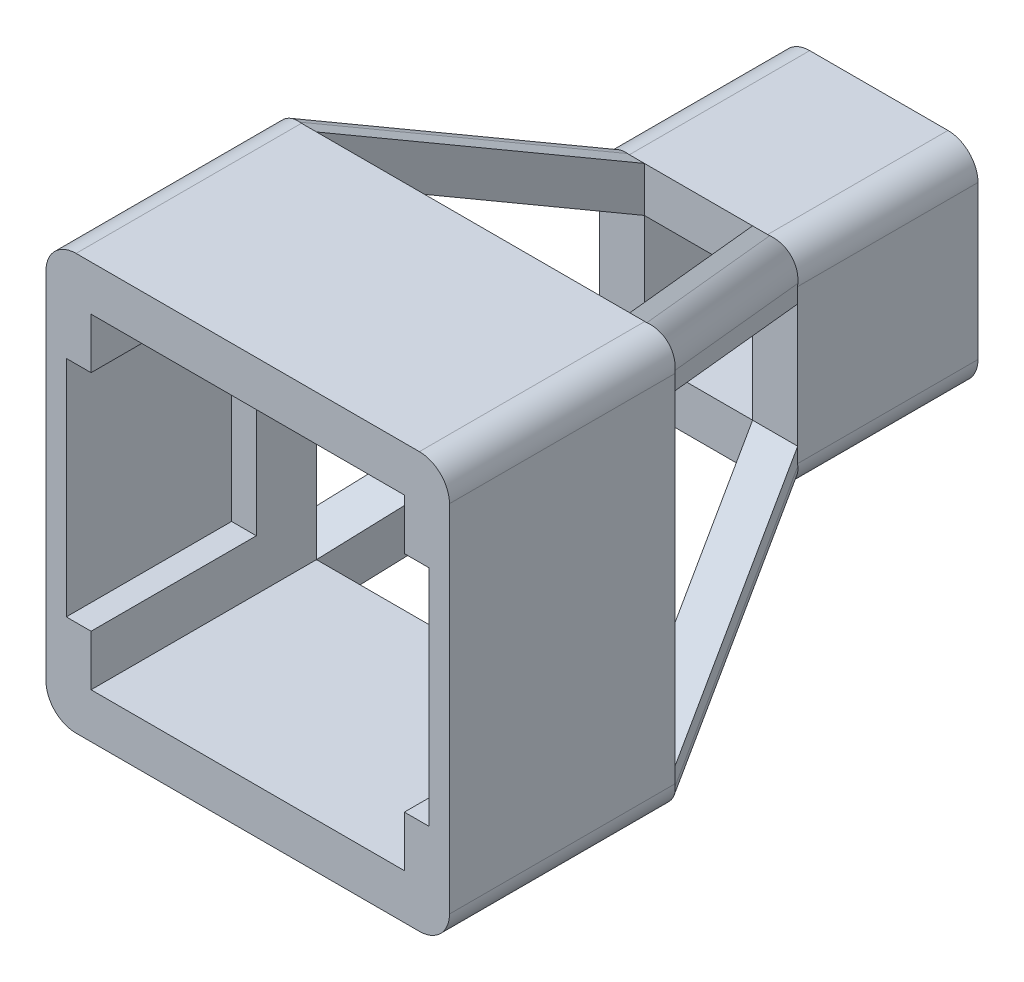
SolidWorks part; units mm, degrees
ref_plane "正面" through (0, 0, 0) normal (0, 0, 1) x (1, 0, 0)
ref_plane "平面" through (0, 0, 0) normal (0, 1, 0) x (1, 0, 0)
ref_plane "右側面" through (0, 0, 0) normal (1, 0, 0) x (0, 0, -1)
sketch "ｽｹｯﾁ1" plane through (0, 0, 0) normal (0, 0, 1) x (1, 0, 0)
  line L0 (6.6, 7.1) -> (-6.6, 7.1)
  line L1 (3.6, -4.1) -> (-3.6, -4.1)
  line L2 (3.6, -4.1) -> (3.6, 4.1)
  line L3 (3.6, 4.1) -> (-3.6, 4.1)
  line L4 (-3.6, -4.1) -> (-3.6, 4.1)
  line L5 (3.6, -4.1) -> (-3.6, 4.1) construction
  line L6 (3.6, 4.1) -> (-3.6, -4.1) construction
  line L7 (-6.6, -7.1) -> (-6.6, 7.1)
  line L8 (6.6, -7.1) -> (-6.6, -7.1)
  line L9 (6.6, -7.1) -> (6.6, 7.1)
  point P0 (0, 0)
  dimension "D1" = 7.2
  dimension "D2" = 8.2
  dimension "D3" = 3
extrude "ﾎﾞｽ - 押し出し1" add sketch "ｽｹｯﾁ1" along normal blind 12
ref_plane "平面1" through (0, 0, 27) normal (0, 0, 1) x (1, 0, 0)
sketch "ｽｹｯﾁ2" plane through (0, 0, 27) normal (0, 0, 1) x (1, 0, 0)
  line L1 (13.425, -14.65) -> (-13.425, -14.65)
  line L2 (13.425, -14.65) -> (13.425, 13)
  line L3 (13.425, 13) -> (-13.425, 13)
  line L4 (-13.425, -14.65) -> (-13.425, 13)
  line L5 (13.425, -14.65) -> (-13.425, 13) construction
  line L6 (13.425, 13) -> (-13.425, -14.65) construction
  line L7 (10.425, -11.65) -> (-10.425, -11.65)
  line L8 (10.425, -11.65) -> (10.425, 10)
  line L9 (10.425, 10) -> (-10.425, 10)
  line L10 (-10.425, -11.65) -> (-10.425, 10)
  line L11 (10.425, -11.65) -> (-10.425, 10) construction
  line L12 (10.425, 10) -> (-10.425, -11.65) construction
  line L13 (-13.425, 13) -> (-10.425, 13)
  line L14 (-13.425, 13) -> (-13.425, 10)
  line L15 (-13.425, 10) -> (-10.425, 10)
  line L16 (-10.425, 13) -> (-10.425, 10)
  line L17 (-13.425, 13) -> (-10.425, 10) construction
  line L18 (-13.425, 10) -> (-10.425, 13) construction
  line L19 (13.425, 13) -> (10.425, 13)
  line L20 (13.425, 13) -> (13.425, 10)
  line L21 (13.425, 10) -> (10.425, 10)
  line L22 (10.425, 13) -> (10.425, 10)
  line L23 (13.425, 13) -> (10.425, 10) construction
  line L24 (13.425, 10) -> (10.425, 13) construction
  line L25 (10.425, -11.65) -> (13.425, -11.65)
  line L26 (10.425, -11.65) -> (10.425, -14.65)
  line L27 (10.425, -14.65) -> (13.425, -14.65)
  line L28 (13.425, -11.65) -> (13.425, -14.65)
  line L29 (10.425, -11.65) -> (13.425, -14.65) construction
  line L30 (10.425, -14.65) -> (13.425, -11.65) construction
  line L31 (-13.425, -14.65) -> (-10.425, -14.65)
  line L32 (-13.425, -14.65) -> (-13.425, -11.65)
  line L33 (-13.425, -11.65) -> (-10.425, -11.65)
  line L34 (-10.425, -14.65) -> (-10.425, -11.65)
  line L35 (-13.425, -14.65) -> (-10.425, -11.65) construction
  line L36 (-13.425, -11.65) -> (-10.425, -14.65) construction
  point P0 (0, 0)
  point P5 (0, 0)
  point P6 (0, 0)
  point P11 (0, 0)
  point P14 (-11.925, 11.5)
  point P15 (0, 0)
  point P18 (11.925, 11.5)
  point P21 (11.925, -13.15)
  point P24 (-11.925, -13.15)
  point P25 (0, 0)
  point P26 (0, 0)
  point P28 (0, -0.825)
  dimension "D1" = 20.85
  dimension "D2" = 21.65
  dimension "D3" = 3
  dimension "D4" = 3
  dimension "D5" = 10
sketch "ｽｹｯﾁ3" plane through (0, 0, 12) normal (0, 0, 1) x (1, 0, 0)
  line L1 (-6.6, 7.1) -> (-3.6, 7.1)
  line L2 (-6.6, 7.1) -> (-6.6, 4.1)
  line L3 (-6.6, 4.1) -> (-3.6, 4.1)
  line L4 (-3.6, 7.1) -> (-3.6, 4.1)
  line L5 (-6.6, 7.1) -> (-3.6, 4.1) construction
  line L6 (-6.6, 4.1) -> (-3.6, 7.1) construction
  line L7 (6.6, 7.1) -> (3.6, 7.1)
  line L8 (6.6, 7.1) -> (6.6, 4.1)
  line L9 (6.6, 4.1) -> (3.6, 4.1)
  line L10 (3.6, 7.1) -> (3.6, 4.1)
  line L11 (6.6, 7.1) -> (3.6, 4.1) construction
  line L12 (6.6, 4.1) -> (3.6, 7.1) construction
  line L13 (6.6, -7.1) -> (3.6, -7.1)
  line L14 (6.6, -7.1) -> (6.6, -4.1)
  line L15 (6.6, -4.1) -> (3.6, -4.1)
  line L16 (3.6, -7.1) -> (3.6, -4.1)
  line L17 (6.6, -7.1) -> (3.6, -4.1) construction
  line L18 (6.6, -4.1) -> (3.6, -7.1) construction
  line L19 (-6.6, -7.1) -> (-3.6, -7.1)
  line L20 (-6.6, -7.1) -> (-6.6, -4.1)
  line L21 (-6.6, -4.1) -> (-3.6, -4.1)
  line L22 (-3.6, -7.1) -> (-3.6, -4.1)
  line L23 (-6.6, -7.1) -> (-3.6, -4.1) construction
  line L24 (-6.6, -4.1) -> (-3.6, -7.1) construction
  point P4 (-5.1, 5.6)
  point P11 (5.1, 5.6)
  point P18 (5.1, -5.6)
  point P25 (-5.1, -5.6)
loft "ﾛﾌﾄ1" add section "ｽｹｯﾁ3" section "ｽｹｯﾁ2" connector at (-3.6, -4.1, 12) connector at (-10.425, -11.65, 27)
loft "ﾛﾌﾄ2" add section "ｽｹｯﾁ3<4>" section "ｽｹｯﾁ2<3>" connector at (3.6, -7.1, 12) connector at (10.425, -14.65, 27)
sketch "ｽｹｯﾁ3<4>" plane through (0, 0, 12) normal (0, 0, 1) x (1, 0, 0) same geometry as "ｽｹｯﾁ3"
sketch "ｽｹｯﾁ2<3>" plane through (0, 0, 27) normal (0, 0, 1) x (1, 0, 0) same geometry as "ｽｹｯﾁ2"
loft "ﾛﾌﾄ3" add section "ｽｹｯﾁ3<5>" section "ｽｹｯﾁ2<4>" connector at (3.6, 4.1, 12) connector at (10.425, 10, 27)
sketch "ｽｹｯﾁ3<5>" plane through (0, 0, 12) normal (0, 0, 1) x (1, 0, 0) same geometry as "ｽｹｯﾁ3"
sketch "ｽｹｯﾁ2<4>" plane through (0, 0, 27) normal (0, 0, 1) x (1, 0, 0) same geometry as "ｽｹｯﾁ2"
loft "ﾛﾌﾄ5" add section "ｽｹｯﾁ2<6>" section "ｽｹｯﾁ3<7>" connector at (-13.425, 10, 27) connector at (-6.6, 4.1, 12)
sketch "ｽｹｯﾁ2<6>" plane through (0, 0, 27) normal (0, 0, 1) x (1, 0, 0) same geometry as "ｽｹｯﾁ2"
sketch "ｽｹｯﾁ3<7>" plane through (0, 0, 12) normal (0, 0, 1) x (1, 0, 0) same geometry as "ｽｹｯﾁ3"
extrude "ﾎﾞｽ - 押し出し2" add sketch "ｽｹｯﾁ2<8>" along normal blind 15 contours L9 L10 L7 L8 | L4 L3 L2 L1
sketch "ｽｹｯﾁ2<8>" plane through (0, 0, 27) normal (0, 0, 1) x (1, 0, 0) same geometry as "ｽｹｯﾁ2"
sketch "ｽｹｯﾁ4" plane through (0, 0, 42) normal (0, 0, 1) x (1, 0, 0)
  line L0 (-10.425, -11.65) -> (-10.425, 10) construction
  line L1 (-10.425, 6.625) -> (-12.075, 6.625)
  line L2 (-10.425, 6.625) -> (-10.425, -8.275)
  line L3 (-10.425, -8.275) -> (-12.075, -8.275)
  line L4 (-12.075, 6.625) -> (-12.075, -8.275)
  line L5 (-10.425, 6.625) -> (-12.075, -8.275) construction
  line L6 (-10.425, -8.275) -> (-12.075, 6.625) construction
  line L7 (10.425, -11.65) -> (10.425, 10) construction
  line L8 (10.425, 6.625) -> (12.075, 6.625)
  line L9 (10.425, 6.625) -> (10.425, -8.275)
  line L10 (10.425, -8.275) -> (12.075, -8.275)
  line L11 (12.075, 6.625) -> (12.075, -8.275)
  line L12 (10.425, 6.625) -> (12.075, -8.275) construction
  line L13 (10.425, -8.275) -> (12.075, 6.625) construction
  line L15 (-40.275, -0.825) -> (13.425, -0.825) construction
  line L18 (10.425, 10) -> (-10.425, 10) construction
  line L19 (10.425, -11.65) -> (-10.425, -11.65) construction
  point P4 (-11.25, -0.825)
  point P11 (11.25, -0.825)
  point P17 (0, 0)
  point P21 (-13.425, -0.825)
  dimension "D1" = 1.65
  dimension "D2" = 14.9
extrude "ｶｯﾄ - 押し出し1" cut sketch "ｽｹｯﾁ4" against normal blind 11
chamfer "面取り1" distance 0.4 angle 45 4 edges at (0, -4.1, 0) (-3.6, 0, 0) (0, 4.1, 0) (3.6, 0, 0)
fillet "ﾌｨﾚｯﾄ1" radius 2 12 edges at (6.6, 7.1, 6)
